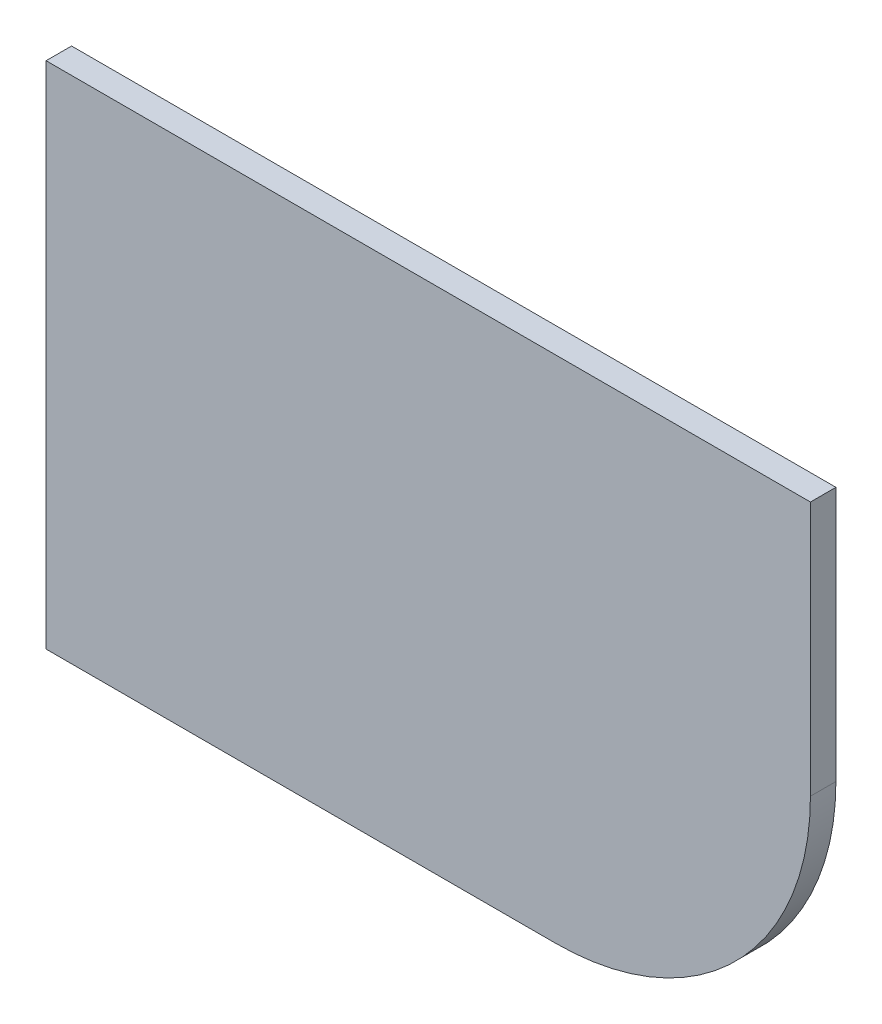
SolidWorks part; units mm, degrees
ref_plane "Front Plane" through (0, 0, 0) normal (0, 0, 1) x (1, 0, 0)
ref_plane "Top Plane" through (0, 0, 0) normal (0, 1, 0) x (1, 0, 0)
ref_plane "Right Plane" through (0, 0, 0) normal (1, 0, 0) x (0, 0, -1)
sketch "Sketch1" plane through (0, 0, 0) normal (0, 0, 1) x (1, 0, 0)
  line L0 (0, 200) -> (0, 0)
  line L1 (0, 200) -> (300, 200)
  line L2 (300, 200) -> (300, 100)
  line L3 (200, 0) -> (0, 0)
  arc A0 (300, 100) -> (200, 0) centre (200, 100) cw
  point P6 (0, 0)
  point P7 (0, 0)
  point P9 (8204.8419, 0)
  point P10 (6188.7221, -3528.2096)
  point P11 (5000, 0)
  point P12 (-7.7878, 126.6434)
  point P13 (0, 0)
  dimension "D1" = 300
  dimension "D3" = 100
  dimension "D2" = 200
extrude "Boss-Extrude1" add sketch "Sketch1" along normal mid plane 10
sketch "Sketch6" plane through (0, 0, -5) normal (0, 0, -1) x (-1, 0, 0)
  line L0 (0, 200) -> (0, 0) construction
  line L1 (0, 0) -> (-200, 0) construction
  circle A0 centre (-225, 140) radius 4
  circle A1 centre (-150, 90) radius 4
  circle A2 centre (-60, 140) radius 4
  circle A3 centre (-75, 40) radius 4
  point P8 (-388.0379, 160.8095)
  point P9 (-527.5982, 322.4847)
  point P10 (-266.5952, 105.5519)
  point P11 (-215.584, 257.0283)
  point P14 (0, 0)
  point P17 (-437.4413, 241.1375)
  point P18 (-450.1605, 272.8337)
  point P19 (-379.6834, 245.8284)
  point P20 (-151.7271, 255)
  point P21 (-39.2801, 175)
  dimension "D1" = 8
  dimension "D2" = 75
  dimension "D3" = 40
  dimension "D4" = 50
  dimension "D5" = 75
  dimension "D6" = 100
  dimension "D7" = 50
  dimension "D8" = 75
  dimension "D9" = 15
extrude "Cut-Extrude1" cut sketch "Sketch6" against normal offset from surface (9 mm away) 1 up to face at (164.1421, 95.8579, 5)
